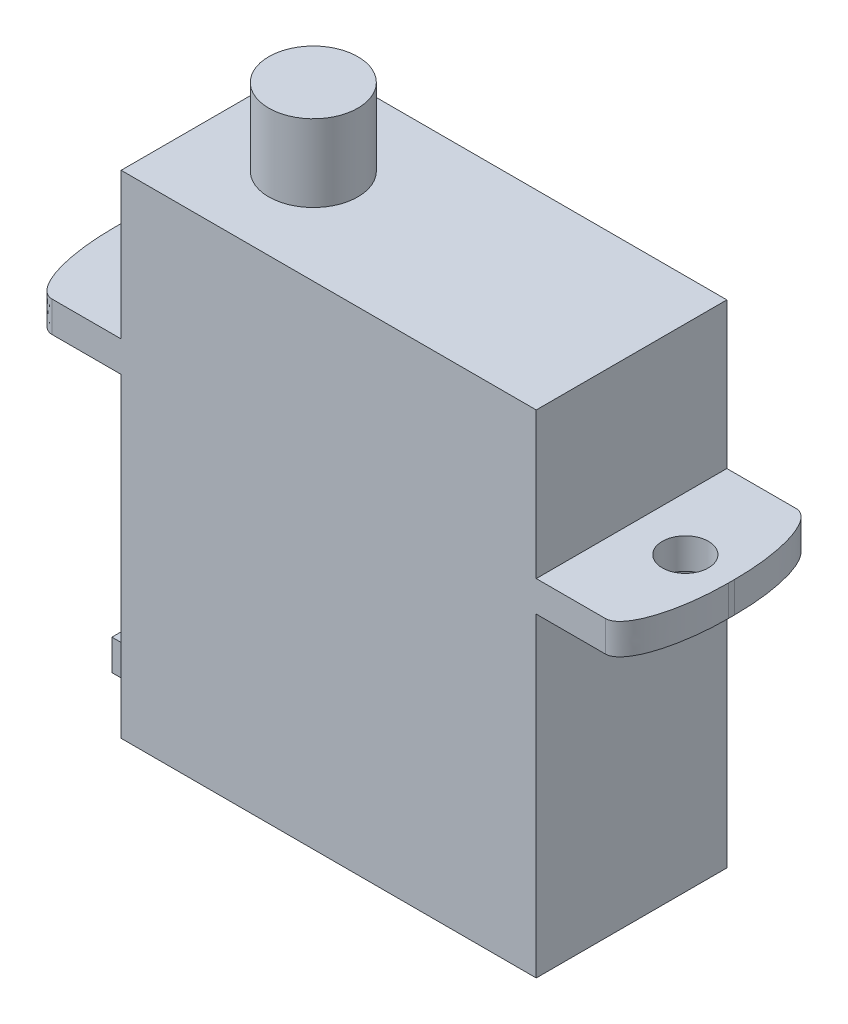
SolidWorks part; units mm, degrees
material "ABS"
ref_plane "前视基准面" through (0, 0, 0) normal (0, 0, 1) x (1, 0, 0)
ref_plane "上视基准面" through (0, 0, 0) normal (0, 1, 0) x (1, 0, 0)
ref_plane "右视基准面" through (0, 0, 0) normal (1, 0, 0) x (0, 0, -1)
sketch "草图1" plane through (0, 0, 0) normal (0, 1, 0) x (1, 0, 0)
  line L1 (0, 0) -> (-13.5, 0)
  line L2 (0, 0) -> (0, 6.2)
  line L3 (0, 6.2) -> (-13.5, 6.2)
  line L4 (-13.5, 0) -> (-13.5, 6.2)
  dimension "D1" = 13.5
  dimension "D2" = 6.2
extrude "凸台-拉伸1" add sketch "草图1" along normal blind 16
sketch "草图2" plane through (0, 0, 0) normal (0, 0, 1) x (1, 0, 0)
  line L0 (0, 16) -> (0, 0) construction
  line L1 (0, 11.25) -> (3.25, 11.25)
  line L2 (0, 11.25) -> (0, 10.25)
  line L3 (0, 10.25) -> (3.25, 10.25)
  line L4 (3.25, 11.25) -> (3.25, 10.25)
  line L5 (-13.5, 0) -> (0, 0) construction
  line L6 (-6.75, 0) -> (-6.75, 16)
  line L7 (-13.5, 16) -> (0, 16) construction
  line L8 (-16.75, 11.25) -> (-16.75, 10.25)
  line L9 (-13.5, 10.25) -> (-16.75, 10.25)
  line L10 (-13.5, 11.25) -> (-13.5, 10.25)
  line L11 (-13.5, 11.25) -> (-16.75, 11.25)
  line M5 (0, 0) -> (0, 16)
  dimension "D1" = 3.25
  dimension "D2" = 1
  dimension "D3" = 10.25
extrude "凸台-拉伸2" add sketch "草图2" against normal blind 6.2 contours L4 L1 L3 M5 | L9 L8 L11 L10 region at (1.625, 10.75, 0)
sketch "草图3" plane through (0, 11.25, 0) normal (0, 1, 0) x (1, 0, 0)
  line L0 (-16.75, 6.2) -> (-16.75, 0) construction
  line L1 (3.25, 6.2) -> (3.25, 0) construction
  circle A0 centre (-15.25, 3.1) radius 0.75
  circle A1 centre (1.75, 3.1) radius 0.75
  point P6 (-16.75, 3.1)
  dimension "D1" = 1.5
  dimension "D2" = 1.5
  dimension "D3" = 1.5
  dimension "D4" = 1.5
extrude "切除-拉伸1" cut sketch "草图3" against normal through all
sketch "草图4" plane through (0, 16, 0) normal (0, 1, 0) x (1, 0, 0)
  line L0 (-13.5, 6.2) -> (-13.5, 0) construction
  circle A0 centre (-10.35, 3.1) radius 1.45
  dimension "D1" = 2.9
  dimension "D2" = 3.15
extrude "凸台-拉伸3" add sketch "草图4" along normal blind 2.5
fillet "圆角1" radius 1 2 edges at (3.25, 10.75, 0) (-16.75, 10.75, -6.2) second distance 3 first distance on face at (-6.75, 9.8333, 0) first distance on face at (-6.75, 9.8333, -6.2)
fillet "圆角2" radius 3 2 edges at (-16.75, 10.75, 0) (3.25, 10.75, -6.2) second distance 1 first distance on face at (-16.75, 10.875, -2.4) first distance on face at (3.25, 10.875, -5.4)
sketch "草图5" plane through (-13.5, 0, 0) normal (-1, 0, 0) x (0, 0, 1)
  line L0 (-6.2, 0) -> (0, 0) construction
  line L1 (-4.7, 0) -> (-1.7, 0)
  line L2 (-4.7, 0) -> (-4.7, 1)
  line L3 (-4.7, 1) -> (-1.7, 1)
  line L4 (-1.7, 0) -> (-1.7, 1)
  dimension "D1" = 1
  dimension "D2" = 3
  dimension "D3" = 1.7
extrude "凸台-拉伸4" add sketch "草图5" along normal blind 2
